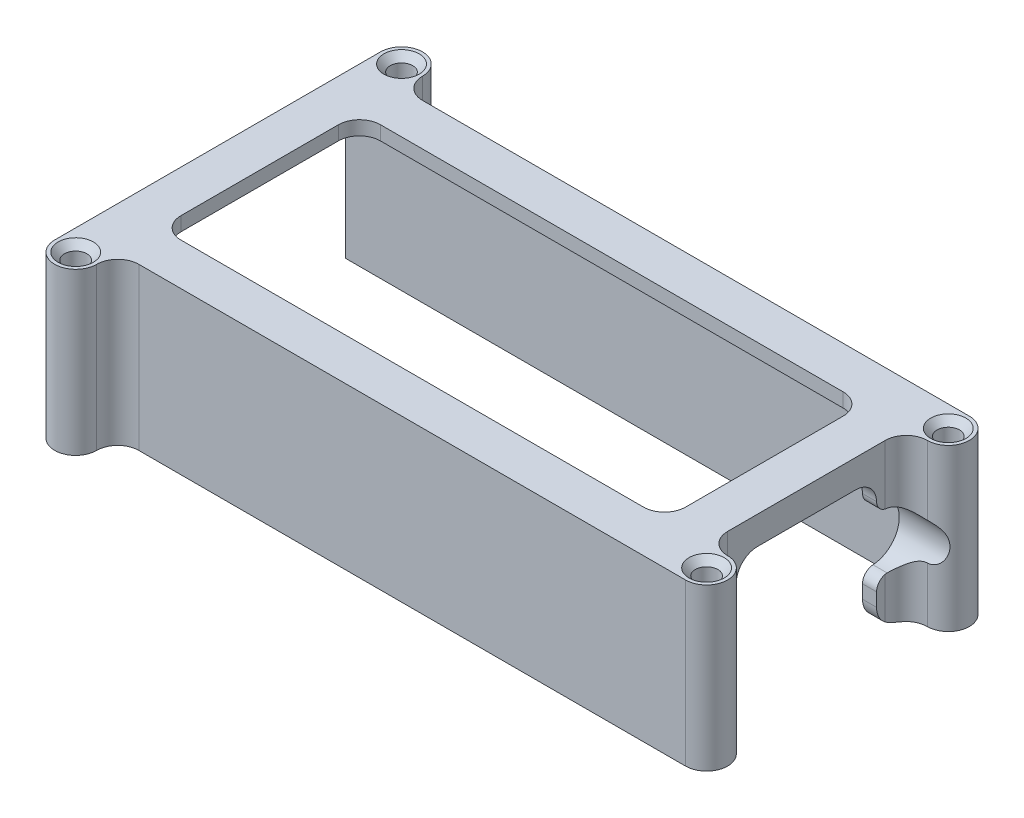
SolidWorks part; units mm, degrees
ref_plane "Front Plane" through (0, 0, 0) normal (0, 0, 1) x (1, 0, 0)
ref_plane "Top Plane" through (0, 0, 0) normal (0, 1, 0) x (1, 0, 0)
ref_plane "Right Plane" through (0, 0, 0) normal (1, 0, 0) x (0, 0, -1)
sketch "Sketch1" plane through (0, 0, 0) normal (0, 1, 0) x (1, 0, 0)
  line L0 (63.5, 28.956) -> (66.675, 32.131) construction
  line L1 (-63.5, -28.956) -> (63.5, -28.956)
  line L2 (-63.5, -28.956) -> (-63.5, 28.956)
  line L3 (-63.5, 28.956) -> (63.5, 28.956)
  line L4 (63.5, -28.956) -> (63.5, 28.956)
  line L5 (-63.5, -28.956) -> (63.5, 28.956) construction
  line L6 (-63.5, 28.956) -> (63.5, -28.956) construction
  line L7 (-66.675, -32.131) -> (66.675, -32.131)
  line L8 (-66.675, -32.131) -> (-66.675, 32.131)
  line L9 (-66.675, 32.131) -> (66.675, 32.131)
  line L10 (66.675, -32.131) -> (66.675, 32.131)
  line L11 (-66.675, -32.131) -> (66.675, 32.131) construction
  line L12 (-66.675, 32.131) -> (66.675, -32.131) construction
  line L13 (63.5, -28.956) -> (66.675, -32.131) construction
  point P0 (0, 0)
  point P6 (0, 0)
  dimension "D1" = 57.912
  dimension "D2" = 127
  dimension "D3" = 3.175
extrude "Boss-Extrude1" add sketch "Sketch1" along normal blind 33.3375
sketch "Sketch2" plane through (-66.675, 0, 0) normal (-1, 0, 0) x (0, 0, 1)
  line L0 (-32.131, 0) -> (32.131, 0) construction
  line L1 (-15.875, -30.1625) -> (15.875, -30.1625)
  line L2 (-15.875, -30.1625) -> (-15.875, 30.1625)
  line L3 (-15.875, 30.1625) -> (15.875, 30.1625)
  line L4 (15.875, -30.1625) -> (15.875, 30.1625)
  line L5 (-15.875, -30.1625) -> (15.875, 30.1625) construction
  line L6 (-15.875, 30.1625) -> (15.875, -30.1625) construction
  point P0 (0, 0)
  dimension "D1" = 31.75
  dimension "D2" = 30.1625
extrude "Cut-Extrude1" cut sketch "Sketch2" against normal through all
sketch "Sketch3" plane through (0, 33.3375, 0) normal (0, 1, 0) x (1, 0, 0)
  line L0 (-66.675, 32.131) -> (-57.15, 22.606) construction
  line L1 (57.15, -22.606) -> (-57.15, -22.606)
  line L2 (57.15, -22.606) -> (57.15, 22.606)
  line L3 (57.15, 22.606) -> (-57.15, 22.606)
  line L4 (66.675, -32.131) -> (66.675, 32.131)
  line L5 (66.675, 32.131) -> (-66.675, 32.131)
  line L6 (-66.675, 32.131) -> (-66.675, -32.131)
  line L7 (-66.675, -32.131) -> (66.675, -32.131)
  line L8 (66.675, -32.131) -> (66.675, 32.131)
  line L9 (66.675, 32.131) -> (-66.675, 32.131)
  line L10 (-66.675, 32.131) -> (-66.675, -32.131)
  line L11 (-66.675, -32.131) -> (66.675, -32.131)
  line L12 (-57.15, -22.606) -> (-57.15, 22.606)
  line L13 (57.15, -22.606) -> (-57.15, 22.606) construction
  line L14 (57.15, 22.606) -> (-57.15, -22.606) construction
  line L15 (-66.675, -32.131) -> (-57.15, -22.606) construction
  line L16 (63.5, 28.956) -> (-63.5, 28.956) construction
  point P2 (0, 0)
  dimension "D2" = 6.35
  dimension "D1" = 0
extrude "Boss-Extrude2" add sketch "Sketch3" along normal blind 3.175
sketch "Sketch4" plane through (0, 36.5125, 0) normal (0, 1, 0) x (1, 0, 0)
  line L0 (66.675, -32.131) -> (66.675, 32.131) construction
  line L1 (71.4375, 32.131) -> (66.675, 32.131)
  line L2 (66.675, 32.131) -> (66.675, 17.8435)
  circle A0 centre (71.4375, 27.3685) radius 1.27 construction
  arc A1 (71.4375, 32.131) -> (71.4375, 22.606) centre (71.4375, 27.3685) cw
  arc A2 (66.675, 17.8435) -> (71.4375, 22.606) centre (71.4375, 17.8435) cw
  dimension "D1" = 4.7625
  dimension "D2" = 2.54
extrude "Boss-Extrude3" add sketch "Sketch4" against normal up to surface (36.5125 mm away) up to face at (0, 0, -23.2092)
ref_axis "Axis1" through (71.4375, 0, -27.3685) along (0, 1, 0)
ref_plane "Plane1" through (71.4375, 0, 0) normal (1, 0, 0) x (0, 1, 0)
sketch "Sketch5" plane through (71.4375, 0, 0) normal (1, 0, 0) x (0, 1, 0)
  line L0 (0, -29.9085) -> (34.925, -29.9085)
  line L1 (34.925, -29.9085) -> (36.5125, -31.3632)
  line L2 (36.5125, -32.131) -> (36.5125, -22.606) construction
  line L3 (36.5125, -31.3632) -> (36.5125, -27.3685)
  line L4 (36.5125, -27.3685) -> (0, -27.3685) construction
  line L5 (0, -27.3685) -> (36.5125, -27.3685) construction
  line L6 (0, -27.3685) -> (0, -29.9085)
  line L7 (0, -22.606) -> (0, -32.131) construction
  line L8 (36.5125, -27.3685) -> (0, -27.3685)
  dimension "D1" = 5.08
  dimension "D2" = 42.5
  dimension "D3" = 1.5875
revolve "Cut-Revolve1" cut sketch "Sketch5" angle 360 about L8
sketch "Sketch6" plane through (0, 36.5125, 0) normal (0, 1, 0) x (1, 0, 0)
  line L0 (-66.675, 32.131) -> (-66.675, -32.131) construction
  line L1 (-66.675, 36.8935) -> (-66.675, 32.131)
  line L2 (-66.675, 32.131) -> (-52.3875, 32.131)
  line L3 (71.4375, 32.131) -> (-66.675, 32.131) construction
  circle A0 centre (-61.9125, 36.8935) radius 3.9947 construction
  arc A1 (-57.15, 36.8935) -> (-66.675, 36.8935) centre (-61.9125, 36.8935) ccw
  arc A2 (-52.3875, 32.131) -> (-57.15, 36.8935) centre (-52.3875, 36.8935) cw
  arc A3 (71.4375, 22.606) -> (71.4375, 32.131) centre (71.4375, 27.3685) ccw construction
  circle A5 centre (71.4375, 27.3685) radius 3.9947 construction
  arc A6 (-61.9125, 32.131) -> (-57.15, 36.8935) centre (-61.9125, 36.8935) ccw construction
  arc A7 (-66.675, 36.8935) -> (-61.9125, 32.131) centre (-61.9125, 36.8935) ccw construction
  circle A8 centre (-61.9125, 36.8935) radius 2.54
  circle A9 centre (71.4375, 27.3685) radius 2.54 construction
extrude "Boss-Extrude4" add sketch "Sketch6" against normal up to surface (36.5125 mm away) up to face at (71.4375, 0, -24.8285)
ref_axis "Axis2" through (-61.9125, 0, -36.8935) along (0, 1, 0)
ref_plane "Plane2" through (-61.9125, 0, 0) normal (-1, 0, 0) x (0, 1, 0)
sketch "Sketch7" plane through (-61.9125, 0, 0) normal (-1, 0, 0) x (0, 1, 0)
  line L0 (34.925, 39.4335) -> (36.5125, 40.8882)
  line L1 (0, 36.8935) -> (36.5125, 36.8935) construction
  line L2 (36.5125, 36.8935) -> (36.5125, 41.656) construction
  line L3 (36.5125, 40.8882) -> (36.5125, 36.8935)
  line L4 (36.5125, 34.3535) -> (36.5125, 39.4335) construction
  line L5 (36.5125, 36.8935) -> (34.925, 36.8935)
  line L6 (36.5125, 31.3632) -> (34.925, 29.9085) construction
  line L7 (34.925, 36.8935) -> (34.925, 39.4335)
  line L8 (32.1531, 36.8935) -> (34.925, 39.4335) construction
  line L9 (34.925, 36.8935) -> (32.1531, 36.8935) construction
  line L10 (36.5125, 27.3685) -> (36.5125, 31.3632) construction
  line L11 (0, 27.3685) -> (36.5125, 27.3685) construction
  line L12 (36.5125, 36.8935) -> (36.5125, -32.131) construction
revolve "Cut-Revolve2" cut sketch "Sketch7" angle 360 about L9
mirror "Mirror1" about plane through (0, 0, 0) normal (0, 0, 1) of "Cut-Revolve2", "Boss-Extrude4", "Boss-Extrude3", "Cut-Revolve1"
mirror "Mirror2" [suppressed] about plane through (0, 0, 0) normal (1, 0, 0)
sketch "Sketch8" plane through (-63.5, 0, 0) normal (1, 0, 0) x (0, 0, -1)
  line L8 (-15.875, 0) -> (-15.875, 30.1625)
  line L9 (-15.875, 30.1625) -> (15.875, 30.1625)
  line L10 (15.875, 30.1625) -> (15.875, 0)
  line L11 (15.875, 0) -> (28.956, 0)
  line L12 (28.956, 0) -> (28.956, 33.3375)
  line L13 (28.956, 33.3375) -> (-28.956, 33.3375)
  line L14 (-28.956, 33.3375) -> (-28.956, 0)
  line L15 (-28.956, 0) -> (-15.875, 0)
  line L16 (-15.875, 0) -> (-15.875, 30.1625)
  line L17 (-15.875, 30.1625) -> (15.875, 30.1625)
  line L18 (15.875, 30.1625) -> (15.875, 0)
  line L19 (15.875, 0) -> (28.956, 0)
  line L20 (28.956, 0) -> (28.956, 33.3375)
  line L21 (28.956, 33.3375) -> (-28.956, 33.3375)
  line L22 (-28.956, 33.3375) -> (-28.956, 0)
  line L23 (-28.956, 0) -> (-15.875, 0)
  dimension "D1" = 0
extrude "Cut-Extrude2" cut sketch "Sketch8" against normal through all
fillet "Fillet1" radius 1.5875 5 edges at (63.5, 16.6687, -28.956) (-1.5875, 33.3375, -28.956) (63.5, 16.6687, 28.956) (63.5, 33.3375, 0) (-1.5875, 33.3375, 28.956)
fillet "Fillet2" radius 4.7625 8 edges at (65.0875, 0, 15.875) (65.0875, 0, -15.875) (65.0875, 30.1625, -15.875) (65.0875, 30.1625, 15.875) (-57.15, 34.925, 22.606) (-57.15, 34.925, -22.606) (57.15, 34.925, 22.606) (57.15, 34.925, -22.606)
sketch "Sketch9" plane through (63.5, 0, 0) normal (-1, 0, 0) x (0, 0, 1)
  line L0 (-27.3685, 33.3375) -> (27.3685, 33.3375) construction
  line L1 (28.956, 33.3375) -> (-28.956, 33.3375) construction
  line L2 (28.956, 33.3375) -> (28.956, 0) construction
  line L3 (28.956, 0) -> (-28.956, 0) construction
  line L4 (-28.956, 33.3375) -> (-28.956, 0) construction
  line L5 (28.956, 33.3375) -> (-28.956, 0) construction
  line L6 (28.956, 0) -> (-28.956, 33.3375) construction
  line L7 (17.8435, 16.6688) -> (-17.8435, 16.6687) construction
  line L8 (24.1935, 16.6687) -> (28.956, 16.6687) construction
  circle A0 centre (17.8435, 16.6688) radius 6.35
  circle A1 centre (-17.8435, 16.6687) radius 6.35
  point P0 (0, 16.6687)
  point P13 (0, 16.6687)
  dimension "D1" = 12.7
  dimension "D2" = 4.7625
extrude "Cut-Extrude4" cut sketch "Sketch9" against normal through all
fillet "Fillet3" radius 2.54 4 edges at (65.0875, 22.7059, -15.875) (65.0875, 10.6316, -15.875) (65.0875, 10.6316, 15.875) (65.0875, 22.7059, 15.875)
